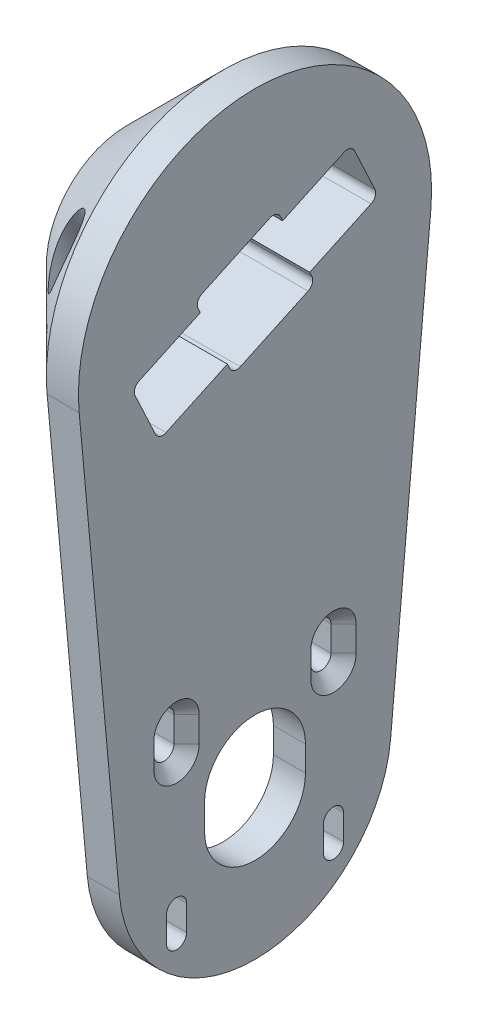
SolidWorks part; units mm, degrees
ref_plane "Front Plane" through (0, 0, 0) normal (0, 0, 1) x (1, 0, 0)
ref_plane "Top Plane" through (0, 0, 0) normal (0, 1, 0) x (1, 0, 0)
ref_plane "Right Plane" through (0, 0, 0) normal (1, 0, 0) x (0, 0, -1)
sketch "Sketch1" plane through (0, 0, 0) normal (1, 0, 0) x (0, 0, -1)
  line L0 (4.3532, 11.9603) -> (-11.9603, 4.3532)
  line L1 (4.3532, 11.9603) -> (11.9603, -4.3532)
  line L2 (-11.9603, 4.3532) -> (-4.3532, -11.9603)
  line L3 (11.9603, -4.3532) -> (-4.3532, -11.9603)
  line L4 (4.3532, 11.9603) -> (-4.3532, -11.9603) construction
  line L5 (-11.9603, 4.3532) -> (11.9603, -4.3532) construction
  line L6 (0, 0) -> (0, -85) construction
  line L7 (-34.8534, -3.2) -> (-26.8869, -89.9686)
  line L8 (26.8869, -89.9686) -> (34.8534, -3.2)
  line L9 (0, -85) -> (0, -103.9417) construction
  arc A0 (34.8534, -3.2) -> (-34.8534, -3.2) centre (0, 0) ccw
  arc A1 (-26.8869, -89.9686) -> (26.8869, -89.9686) centre (0, -87.5) ccw
  dimension "D1" = 2.5
  dimension "D2" = 70
  dimension "D6" = 85
  dimension "D7" = 27
  dimension "D3" = 18
  dimension "D4" = 18
  dimension "D5" = 25
extrude "Boss-Extrude1" add sketch "Sketch1" along normal blind 6.35 contours L7 A0 L1 L3 L2 L0 region at (0, -38.184, 0)
sketch "Sketch17" plane through (0, 0, 0) normal (-1, 0, 0) x (0, 0, 1)
  line L2 (-34.8534, -3.2) -> (-26.8869, -89.9686)
  line L3 (26.8869, -89.9686) -> (34.8534, -3.2)
  line L4 (-34.8534, -3.2) -> (-26.8869, -89.9686)
  line L6 (26.8869, -89.9686) -> (34.8534, -3.2)
  arc A2 (-26.8869, -89.9686) -> (26.8869, -89.9686) centre (0, -87.5) ccw
  arc A3 (-26.8869, -89.9686) -> (26.8869, -89.9686) centre (0, -87.5) ccw
  arc A4 (34.8534, -3.2) -> (-34.8534, -3.2) centre (0, 0) ccw
  arc A8 (34.8534, -3.2) -> (-34.8534, -3.2) centre (0, 0) ccw
  dimension "D1" = 0
sketch "Sketch20" plane through (6.35, 0, 0) normal (1, 0, 0) x (0, 0, -1)
  circle A0 centre (0, 0) radius 35
extrude "Boss-Extrude5" add sketch "Sketch20" along normal blind 19.05
sketch "Sketch21" plane through (0, 0, 0) normal (-1, 0, 0) x (0, 0, 1)
  line L0 (-24.435, 4.3878) -> (-10.8404, -1.9515)
  line L1 (11.9603, 4.3532) -> (4.3532, -11.9603) construction
  line L3 (-4.3532, 11.9603) -> (-11.9603, -4.3532) construction
  line L4 (-4.3532, 11.9603) -> (11.9603, 4.3532) construction
  line L5 (11.9603, 4.3532) -> (10.8404, 1.9515)
  line L7 (-4.3532, 11.9603) -> (-5.4731, 9.5586)
  line L8 (-4.3532, 11.9603) -> (11.9603, 4.3532)
  line L9 (-21.7514, 10.1428) -> (-25.3766, 11.8333) construction
  line L10 (19.0678, -15.8979) -> (5.4731, -9.5586)
  line L11 (19.0678, -15.8979) -> (24.435, -4.3878)
  line L12 (-24.435, 4.3878) -> (-19.0678, 15.8979)
  line L13 (24.435, -4.3878) -> (10.8404, 1.9515)
  line L16 (4.3532, -11.9603) -> (5.4731, -9.5586)
  line L17 (-11.9603, -4.3532) -> (-10.8404, -1.9515)
  line L18 (11.9603, 4.3532) -> (-4.3532, 11.9603)
  line L21 (-10.8404, -1.9515) -> (-11.9603, -4.3532)
  line L24 (-10.8404, -1.9515) -> (-24.435, 4.3878)
  line L27 (-5.4731, 9.5586) -> (-4.3532, 11.9603)
  line L29 (-5.4731, 9.5586) -> (-19.0678, 15.8979)
  line L30 (5.4731, -9.5586) -> (4.3532, -11.9603)
  line L31 (10.8404, 1.9515) -> (11.9603, 4.3532)
  line M13 (-11.9603, -4.3532) -> (-4.3532, 11.9603)
  line M14 (-4.3532, 11.9603) -> (11.9603, 4.3532)
  line M15 (11.9603, 4.3532) -> (4.3532, -11.9603)
  line M16 (4.3532, -11.9603) -> (-11.9603, -4.3532)
  dimension "D1" = 15
  dimension "D2" = 12.7
extrude "Cut-Extrude14" cut sketch "Sketch21" against normal through all contours L29 L12 L0 M13 | M13 M16 M15 M14 | L11 L13 L10 M15 region at (0, 6.9732, -14.9541) region at (0, 0, 0) region at (0, -6.9732, 14.9541)
chamfer "Chamfer1" distance 19.05 angle 45 1 edges at (25.4, 0, -35)
sketch "Sketch22" plane through (0, 5.7551, 2.6836) normal (0, -0.9063, -0.4226) x (-1, 0, 0)
  line L0 (-25.4, -9) -> (0, -9) construction
  line L1 (-25.4, -9) -> (-25.4, -14.6315) construction
  circle A0 centre (-13.4, -16.5) radius 3.175
  dimension "D2" = 12
  dimension "D3" = 6.35
  dimension "D1" = 7.5
extrude "Cut-Extrude15" cut sketch "Sketch22" against normal through all
ref_plane "Plane1" through (0, 10.2866, 4.7967) normal (0, -0.9063, -0.4226) x (-1, 0, 0)
sketch "Sketch24" plane through (0, 10.2866, 4.7967) normal (0, -0.9063, -0.4226) x (-1, 0, 0)
  circle A0 centre (-13.4, -16.5) radius 5
  dimension "D1" = 10
extrude "Cut-Extrude16" cut sketch "Sketch24" against normal through all
sketch "Sketch25" plane through (0, -5.7551, -2.6836) normal (0, 0.9063, 0.4226) x (1, 0, 0)
  circle A0 centre (13.4, -16.5) radius 3.175 construction
  circle A1 centre (13.4, -16.5) radius 3.175
  circle A2 centre (13.4, -16.5) radius 2.3813
  dimension "D1" = 0.7937
extrude "Cut-Extrude17" cut sketch "Sketch25" against normal blind 10 contours A2 region at (13.4, -12.7283, 12.2705)
ref_plane "Plane2" through (0, 0, 0) normal (0, 0.4226, -0.9063) x (-1, 0, 0)
mirror "Mirror1" about plane through (0, 0, 0) normal (0, 0.4226, -0.9063) of "Cut-Extrude15", "Cut-Extrude17", "Cut-Extrude16"
sketch "Sketch19" plane through (6.35, 0, 0) normal (1, 0, 0) x (0, 0, -1)
  line L0 (0, -87.5) -> (0, -82.5)
  line L1 (0, -82.5) -> (15.5563, -66.9437) construction
  line L2 (15.5563, -71.9437) -> (15.5563, -66.9437) construction
  line L3 (13.5563, -71.9437) -> (13.5563, -66.9437)
  line L4 (17.5563, -71.9437) -> (17.5563, -66.9437)
  line L5 (-10, -87.5) -> (-10, -82.5)
  line L6 (10, -87.5) -> (10, -82.5)
  line L7 (0, -85) -> (7.4061, -85) construction
  line L8 (15.5563, -71.9437) -> (0, -87.5) construction
  line L9 (17.5563, -98.0563) -> (17.5563, -103.0563)
  line L10 (13.5563, -98.0563) -> (13.5563, -103.0563)
  line L11 (-17.5563, -71.9437) -> (-17.5563, -66.9437)
  line L12 (-13.5563, -71.9437) -> (-13.5563, -66.9437)
  line L13 (-13.5563, -98.0563) -> (-13.5563, -103.0563)
  line L14 (-17.5563, -98.0563) -> (-17.5563, -103.0563)
  line L15 (-15.5563, -71.9437) -> (0, -87.5) construction
  line L16 (0, -87.5) -> (-15.5563, -103.0563) construction
  line L17 (0, -87.5) -> (15.5563, -103.0563) construction
  arc A2 (-10, -87.5) -> (10, -87.5) centre (0, -87.5) ccw
  arc A3 (17.5563, -103.0563) -> (13.5563, -103.0563) centre (15.5563, -103.0563) cw
  arc A4 (13.5563, -98.0563) -> (17.5563, -98.0563) centre (15.5563, -98.0563) cw
  arc A6 (17.5563, -66.9437) -> (13.5563, -66.9437) centre (15.5563, -66.9437) ccw
  arc A7 (13.5563, -71.9437) -> (17.5563, -71.9437) centre (15.5563, -71.9437) ccw
  arc A8 (-17.5563, -66.9437) -> (-13.5563, -66.9437) centre (-15.5563, -66.9437) cw
  arc A9 (10, -82.5) -> (-10, -82.5) centre (0, -82.5) ccw
  arc A10 (-13.5563, -71.9437) -> (-17.5563, -71.9437) centre (-15.5563, -71.9437) cw
  arc A11 (-13.5563, -98.0563) -> (-17.5563, -98.0563) centre (-15.5563, -98.0563) ccw
  arc A13 (-17.5563, -103.0563) -> (-13.5563, -103.0563) centre (-15.5563, -103.0563) ccw
  point P8 (0, -85)
  dimension "D1" = 82.5
  dimension "D3" = 22
  dimension "D5" = 4
  dimension "D6" = 5
  dimension "D4" = 4
  dimension "D2" = 5
  dimension "D7" = 45
extrude "Cut-Extrude18" cut sketch "Sketch19" against normal blind 10 contours L6 A9 L5 A2 | A10 L12 A8 L11 | L14 A13 L13 A11 | A4 L10 A3 L9 | L4 A6 L3 A7 region at (6.35, -85, 9.6798) region at (6.35, -100.5563, -15.5563) region at (6.35, -69.4437, 15.5563) region at (6.35, -100.5563, 15.5563)
mirror "Mirror2" about plane through (0, 0, 0) normal (1, 0, 0) of bodies 126
delete or keep bodies "Body-Delete/Keep 1" type delete bodies bodies 126
chamfer "Chamfer3" distance 2.5 angle 45 8 edges at (0, -73.9437, 15.5563) (0, -69.4437, 17.5563) (0, -64.9437, 15.5563) (0, -69.4437, 13.5563) (0, -73.9437, -15.5563) (0, -69.4437, -17.5563) (0, -64.9437, -15.5563) (0, -69.4437, -13.5563)
fillet "Fillet1" radius 1.5875 8 edges at (-12.7, -4.3532, -11.9603) (-8.2621, 4.3878, -24.435) (-8.2621, 15.8979, -19.0678) (-12.7, 11.9603, -4.3532) (-12.7, -11.9603, 4.3532) (-8.2621, -15.8979, 19.0678) (-8.2621, -4.3878, 24.435) (-12.7, 4.3532, 11.9603)
sketch "Sketch26" [suppressed] plane through (0, 0, 0) normal (1, 0, 0) x (0, 0, -1)
  line L0 (0, 0) -> (0, 57.119) construction
  line L1 (-25.7469, 27.1204) -> (-36.5305, 44.6181)
  line L2 (-36.5305, 44.6181) -> (-25.7188, 51.2812)
  line L3 (-25.7188, 51.2812) -> (-15.2977, 34.3717)
  line L4 (25.7188, 51.2812) -> (15.2977, 34.3717)
  line L5 (36.5305, 44.6181) -> (25.7188, 51.2812)
  line L6 (25.7469, 27.1204) -> (36.5305, 44.6181)
  line L7 (-23.9889, -130.0736) -> (-18.6587, -109.2177)
  line L8 (-11.6844, -133.2183) -> (-7.4303, -116.573)
  line L9 (-11.6844, -133.2183) -> (-23.9889, -130.0736)
  line L10 (11.6844, -133.2183) -> (7.4303, -116.573)
  line L11 (23.9889, -130.0736) -> (18.6587, -109.2177)
  line L12 (11.6844, -133.2183) -> (23.9889, -130.0736)
  arc A0 (34.8534, -3.2) -> (-34.8534, -3.2) centre (0, 0) ccw construction
  arc A1 (34.8534, -3.2) -> (-11.5473, 33.0403) centre (0, 0) ccw
  arc A2 (-26.0836, 23.3376) -> (-34.8534, -3.2) centre (0, 0) ccw
  arc A3 (-26.0836, 23.3376) -> (-25.7469, 27.1204) centre (-28.4498, 25.4546) ccw
  arc A4 (-11.5473, 33.0403) -> (-15.2977, 34.3717) centre (-12.5948, 36.0375) cw
  arc A5 (11.5473, 33.0403) -> (15.2977, 34.3717) centre (12.5948, 36.0375) ccw
  arc A6 (26.0836, 23.3376) -> (25.7469, 27.1204) centre (28.4498, 25.4546) cw
  arc A7 (-26.8869, -89.9686) -> (26.8869, -89.9686) centre (0, -87.5) ccw construction
  arc A8 (-26.8869, -89.9686) -> (-19.4479, -106.2291) centre (0, -87.5) ccw
  arc A9 (-3.896, -114.2174) -> (26.8869, -89.9686) centre (0, -87.5) ccw
  arc A10 (-18.6587, -109.2177) -> (-19.4479, -106.2291) centre (-21.7348, -108.4315) ccw
  arc A11 (-3.896, -114.2174) -> (-7.4303, -116.573) centre (-4.3542, -117.3592) ccw
  arc A12 (18.6587, -109.2177) -> (19.4479, -106.2291) centre (21.7348, -108.4315) cw
  arc A13 (3.896, -114.2174) -> (7.4303, -116.573) centre (4.3542, -117.3592) cw
  arc A14 (-26.8869, -89.9686) -> (26.8869, -89.9686) centre (0, -87.5) ccw
  arc A15 (34.8534, -3.2) -> (-34.8534, -3.2) centre (0, 0) ccw
  point P11 (-24.4607, 25.0335)
  point P14 (-13.9086, 32.1178)
  point P34 (-6.6856, -113.6592)
  dimension "D2" = 3.175
  dimension "D3" = 3.175
  dimension "D6" = 3.175
  dimension "D7" = 3.175
  dimension "D1" = 12.7
  dimension "D4" = 57.15
  dimension "D5" = 12.7
extrude "Boss-Extrude6" [suppressed] add sketch "Sketch26" against normal blind 5.08
sketch "Sketch27" [suppressed] plane through (-6.35, 0, 0) normal (-1, 0, 0) x (0, 0, 1)
  line L0 (-10, -87.5) -> (-10, -82.5) construction
  line L1 (38.1, -129.8685) -> (-38.1, -129.8685)
  line L2 (38.1, -129.8685) -> (38.1, 47.9315)
  line L3 (38.1, 47.9315) -> (-38.1, 47.9315)
  line L4 (-38.1, -129.8685) -> (-38.1, 47.9315)
  line L5 (5.4731, -9.5586) -> (5.0241, -10.5216) construction
  line L6 (2.9144, -11.2894) -> (-10.5216, -5.0241) construction
  line L7 (5.4731, -9.5586) -> (5.0241, -10.5216)
  line L8 (2.9144, -11.2894) -> (-10.5216, -5.0241)
  line L9 (-2.9144, 11.2894) -> (10.5216, 5.0241) construction
  line L10 (-2.9144, 11.2894) -> (10.5216, 5.0241)
  line L14 (15.9442, -0.4285) -> (10.8404, 1.9515) construction
  line L15 (15.9442, -0.4285) -> (10.8404, 1.9515)
  line L16 (5.0127, -9.3439) -> (4.5637, -10.3069)
  line L17 (3.1291, -10.829) -> (-10.3069, -4.5637)
  line L18 (5.0127, -9.3439) -> (6.5548, -6.0371)
  arc A0 (-10, -87.5) -> (10, -87.5) centre (0, -87.5) ccw construction
  arc A1 (2.9144, -11.2894) -> (5.0241, -10.5216) centre (3.5853, -9.8507) ccw construction
  arc A2 (2.9144, -11.2894) -> (5.0241, -10.5216) centre (3.5853, -9.8507) ccw
  circle A3 centre (2.8571, -7.7595) radius 3.175
  arc A5 (3.1291, -10.829) -> (4.5637, -10.3069) centre (3.5853, -9.8507) ccw
  circle A6 centre (2.5718, -7.0659) radius 3.175
  point P9 (-10, -85)
  point P25 (5.4731, -9.5586)
  dimension "D4" = 3.3498
  dimension "D7" = 44.8685
  dimension "D8" = 6.35
  dimension "D10" = 35.2429
  dimension "D13" = 35.5282
  dimension "D1" = 76.2
  dimension "D2" = 38.1
  dimension "D3" = 177.8
  dimension "D5" = 3.3498
  dimension "D6" = 42.3685
  dimension "D9" = 122.1091
  dimension "D11" = 18
  dimension "D12" = 0.508
  dimension "D14" = 122.8026
  dimension "D15" = 0.6936
  dimension "D16" = 0.2853
sketch "Sketch28" plane through (0, 10.2866, 4.7967) normal (0, 0.9063, 0.4226) x (1, 0, 0)
  line L0 (0, -32.9403) -> (0, 35) construction
  line L1 (0, -32.9403) -> (0, 35)
  line L2 (0, 35) -> (-6.35, 35) construction
  line L3 (0, 35) -> (-6.35, 35)
  circle A0 centre (-13.4, -16.5) radius 3.175 construction
  circle A1 centre (-13.4, -16.5) radius 3.175
  circle A2 centre (-13.4, -16.5) radius 5 construction
  circle A3 centre (-13.4, -16.5) radius 5
  circle A4 centre (-13.4, 16.5) radius 3.175 construction
  circle A5 centre (-13.4, -16.5) radius 2.3813 construction
  circle A6 centre (-13.4, -16.5) radius 2.3813
  dimension "D4" = 4.7625
  dimension "D5" = 33
  dimension "D1" = 13.4
  dimension "D2" = 51.5
  dimension "D3" = 18.5
sketch "Sketch29" plane through (-25.4, 0, 0) normal (-1, 0, 0) x (0, 0, 1)
  line L0 (-7.2798, 15.918) -> (-13.0349, 18.6016) construction
  line L1 (-7.2798, 15.918) -> (-13.0349, 18.6016)
  line L2 (-2.9144, 11.2894) -> (10.5216, 5.0241) construction
  line L3 (10.2024, -22.7977) -> (5.8861, -20.785) construction
  line L4 (10.2024, -22.7977) -> (5.8861, -20.785)
  line L5 (21.9089, 2.307) -> (17.5927, 4.3198) construction
  line L6 (21.9089, 2.307) -> (17.5927, 4.3198)
  arc A0 (34.8534, -3.2) -> (-34.8534, -3.2) centre (0, 0) ccw construction
  arc A1 (34.8534, -3.2) -> (-34.8534, -3.2) centre (0, 0) ccw
  point P5 (3.8036, 8.1568)
  point P6 (14.7916, 31.7208)
  dimension "D1" = 23.65
  dimension "D2" = 27.7
  dimension "D3" = 51.35
sketch "Sketch30" plane through (0, 0, 0) normal (1, 0, 0) x (0, 0, -1)
  line L0 (-10, -87.5) -> (-10, -82.5) construction
  arc A0 (-26.8869, -89.9686) -> (26.8869, -89.9686) centre (0, -87.5) ccw construction
  point P0 (-15.5563, -66.9437)
  point P1 (15.5563, -66.9437)
  point P3 (-20.1757, -105.4427)
  point P5 (-27.4146, -124.9502)
  point P9 (-10, -85)
  point P10 (0, -85)
  point P13 (76.2287, -36.0843)
sketch "Sketch31" plane through (0, 0, 17.5563) normal (0, 0, -1) x (-1, 0, 0)
  line L0 (0, -71.9437) -> (0, -66.9437) construction
  line L1 (0, -71.9437) -> (0, -66.9437)
  line L2 (2.5, -66.9437) -> (2.5, -71.9437) construction
  line L3 (2.5, -66.9437) -> (2.5, -71.9437)
  dimension "D1" = 2.5
equation "\".75i\"=14.27"
